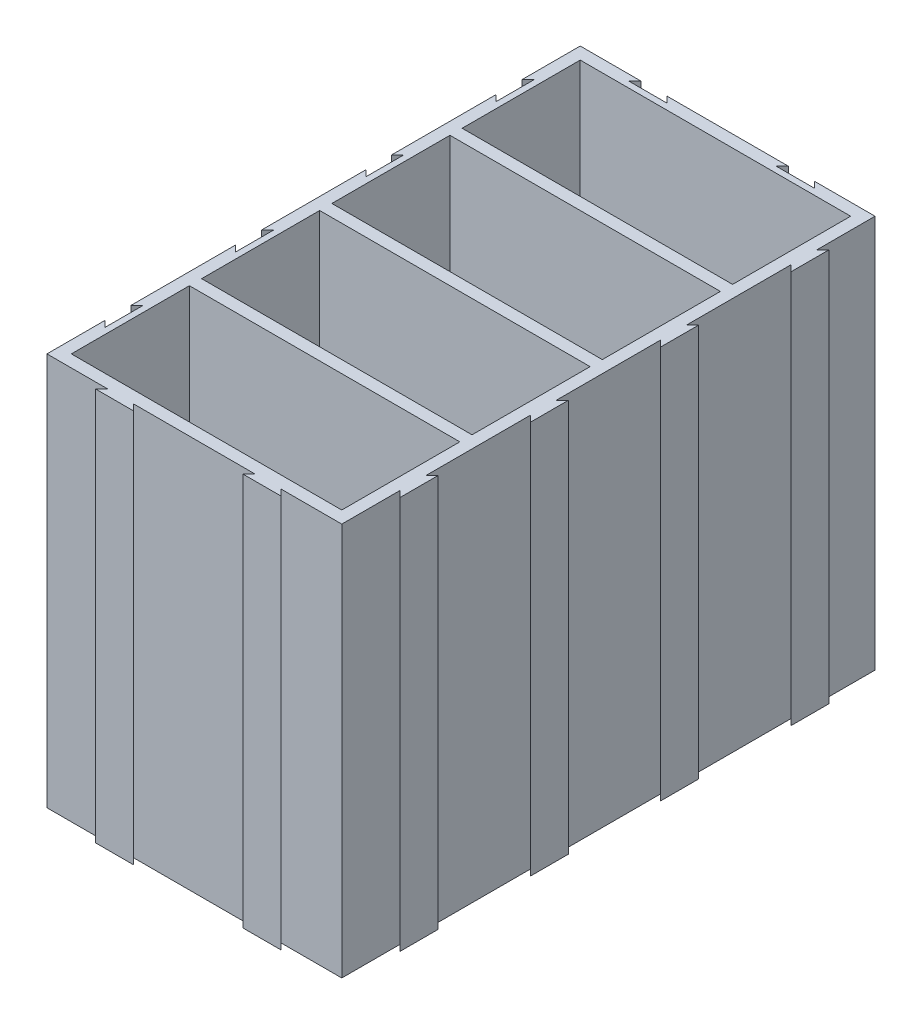
SolidWorks part; units mm, degrees
ref_plane "Спереди" through (0, 0, 0) normal (0, 0, 1) x (1, 0, 0)
ref_plane "Сверху" through (0, 0, 0) normal (0, 1, 0) x (1, 0, 0)
ref_plane "Справа" through (0, 0, 0) normal (1, 0, 0) x (0, 0, -1)
sketch "Эскиз1" plane through (0, 0, 0) normal (0, 1, 0) x (1, 0, 0)
  line L0 (0, 24.2143) -> (0, -22.6471) construction
  line L1 (0, -8.55) -> (0, 8.55) construction
  line L2 (-17.75, 0.8) -> (17.75, 0.8)
  line L3 (-17.75, 0.8) -> (-17.75, 16.3)
  line L4 (-17.75, 16.3) -> (17.75, 16.3)
  line L5 (17.75, 0.8) -> (17.75, 16.3)
  line L6 (-17.75, 0.8) -> (17.75, 16.3) construction
  line L7 (-17.75, 16.3) -> (17.75, 0.8) construction
  line L8 (-17.75, 17.9) -> (17.75, 17.9)
  line L9 (-17.75, 17.9) -> (-17.75, 33.4)
  line L10 (-17.75, 33.4) -> (17.75, 33.4)
  line L11 (17.75, 17.9) -> (17.75, 33.4)
  line L12 (-17.75, 17.9) -> (17.75, 33.4) construction
  line L13 (-17.75, 33.4) -> (17.75, 17.9) construction
  line L14 (-17.75, -16.3) -> (17.75, -16.3)
  line L15 (-17.75, -16.3) -> (-17.75, -0.8)
  line L16 (-17.75, -0.8) -> (17.75, -0.8)
  line L17 (17.75, -16.3) -> (17.75, -0.8)
  line L18 (-17.75, -16.3) -> (17.75, -0.8) construction
  line L19 (-17.75, -0.8) -> (17.75, -16.3) construction
  line L20 (-17.75, -33.4) -> (17.75, -33.4)
  line L21 (-17.75, -33.4) -> (-17.75, -17.9)
  line L22 (-17.75, -17.9) -> (17.75, -17.9)
  line L23 (17.75, -33.4) -> (17.75, -17.9)
  line L24 (-17.75, -33.4) -> (17.75, -17.9) construction
  line L25 (-17.75, -17.9) -> (17.75, -33.4) construction
  line L26 (-19.35, 27.35) -> (-18.55, 28.15)
  line L27 (-19.35, 35) -> (-11.375, 35)
  line L28 (-19.35, 35) -> (-19.35, 27.35)
  line L29 (-19.35, -35) -> (-11.375, -35)
  line L30 (19.35, 35) -> (19.35, 27.35)
  line L31 (-18.55, 28.15) -> (-18.55, 23.15)
  line L32 (-18.55, 23.15) -> (-19.35, 23.95)
  line L33 (20.15, 28.15) -> (20.15, 23.15)
  line L34 (19.35, 27.35) -> (20.15, 28.15)
  line L35 (20.15, 23.15) -> (19.35, 23.95)
  line L36 (20.15, 11.05) -> (20.15, 6.05)
  line L37 (19.35, 10.25) -> (20.15, 11.05)
  line L38 (20.15, 6.05) -> (19.35, 6.85)
  line L39 (20.15, -6.05) -> (20.15, -11.05)
  line L40 (19.35, -6.85) -> (20.15, -6.05)
  line L41 (20.15, -11.05) -> (19.35, -10.25)
  line L42 (20.15, -23.15) -> (20.15, -28.15)
  line L43 (19.35, -23.95) -> (20.15, -23.15)
  line L44 (20.15, -28.15) -> (19.35, -27.35)
  line L45 (-18.55, 11.05) -> (-18.55, 6.05)
  line L46 (-19.35, 10.25) -> (-18.55, 11.05)
  line L47 (-18.55, 6.05) -> (-19.35, 6.85)
  line L48 (-18.55, -6.05) -> (-18.55, -11.05)
  line L49 (-19.35, -6.85) -> (-18.55, -6.05)
  line L50 (-18.55, -11.05) -> (-19.35, -10.25)
  line L51 (-18.55, -23.15) -> (-18.55, -28.15)
  line L52 (-19.35, -23.95) -> (-18.55, -23.15)
  line L53 (-18.55, -28.15) -> (-19.35, -27.35)
  line L54 (-19.35, 23.95) -> (-19.35, 10.25)
  line L55 (-19.35, 6.85) -> (-19.35, -6.85)
  line L56 (-19.35, -10.25) -> (-19.35, -23.95)
  line L57 (-19.35, -27.35) -> (-19.35, -35)
  line L58 (19.35, -27.35) -> (19.35, -35)
  line L59 (19.35, -10.25) -> (19.35, -23.95)
  line L60 (19.35, 6.85) -> (19.35, -6.85)
  line L61 (19.35, 23.95) -> (19.35, 10.25)
  line L62 (11.375, -35) -> (12.175, -35.8)
  line L63 (12.175, -35.8) -> (7.175, -35.8)
  line L64 (7.175, -35.8) -> (7.975, -35)
  line L65 (-7.175, -35.8) -> (-12.175, -35.8)
  line L66 (-12.175, -35.8) -> (-11.375, -35)
  line L67 (-7.975, -35) -> (-7.175, -35.8)
  line L68 (-7.175, 34.2) -> (-12.175, 34.2)
  line L69 (-12.175, 34.2) -> (-11.375, 35)
  line L70 (-7.975, 35) -> (-7.175, 34.2)
  line L71 (12.175, 34.2) -> (7.175, 34.2)
  line L72 (7.175, 34.2) -> (7.975, 35)
  line L73 (11.375, 35) -> (12.175, 34.2)
  line L74 (-7.975, -35) -> (7.975, -35)
  line L75 (11.375, -35) -> (19.35, -35)
  line L76 (11.375, 35) -> (19.35, 35)
  line L77 (-7.975, 35) -> (7.975, 35)
  line L78 (-16.75, 28.15) -> (-3.5, 28.15)
  line L79 (-2.5, 32.4) -> (-2.5, 29.15)
  line L80 (2.5, 32.4) -> (2.5, 29.15)
  line L81 (16.75, 28.15) -> (3.5, 28.15)
  line L82 (-16.75, 23.15) -> (-3.5, 23.15)
  line L83 (-2.5, 18.9) -> (-2.5, 22.15)
  line L84 (2.5, 18.9) -> (2.5, 22.15)
  line L85 (16.75, 23.15) -> (3.5, 23.15)
  line L86 (-2.5, 1.8) -> (-2.5, 5.05)
  line L87 (-16.75, 6.05) -> (-3.5, 6.05)
  line L88 (-2.5, 15.3) -> (-2.5, 12.05)
  line L89 (-16.75, 11.05) -> (-3.5, 11.05)
  line L90 (2.5, 15.3) -> (2.5, 12.05)
  line L91 (16.75, 11.05) -> (3.5, 11.05)
  line L92 (16.75, 6.05) -> (3.5, 6.05)
  line L93 (2.5, 1.8) -> (2.5, 5.05)
  line L94 (-2.5, -15.3) -> (-2.5, -12.05)
  line L95 (-16.75, -11.05) -> (-3.5, -11.05)
  line L96 (-2.5, -1.8) -> (-2.5, -5.05)
  line L97 (-16.75, -6.05) -> (-3.5, -6.05)
  line L98 (2.5, -1.8) -> (2.5, -5.05)
  line L99 (16.75, -6.05) -> (3.5, -6.05)
  line L100 (16.75, -11.05) -> (3.5, -11.05)
  line L101 (2.5, -15.3) -> (2.5, -12.05)
  line L102 (-2.5, -32.4) -> (-2.5, -29.15)
  line L103 (-16.75, -28.15) -> (-3.5, -28.15)
  line L104 (-2.5, -18.9) -> (-2.5, -22.15)
  line L105 (-16.75, -23.15) -> (-3.5, -23.15)
  line L106 (2.5, -18.9) -> (2.5, -22.15)
  line L107 (16.75, -23.15) -> (3.5, -23.15)
  line L108 (16.75, -28.15) -> (3.5, -28.15)
  line L109 (2.5, -32.4) -> (2.5, -29.15)
  arc A0 (-16.75, 33.4) -> (-17.75, 32.4) centre (-16.75, 32.4) ccw
  arc A1 (-2.5, 32.4) -> (-3.5, 33.4) centre (-3.5, 32.4) ccw
  arc A2 (3.5, 33.4) -> (2.5, 32.4) centre (3.5, 32.4) ccw
  arc A3 (2.5, 18.9) -> (3.5, 17.9) centre (3.5, 18.9) ccw
  arc A4 (-3.5, 17.9) -> (-2.5, 18.9) centre (-3.5, 18.9) ccw
  arc A5 (-17.75, 18.9) -> (-16.75, 17.9) centre (-16.75, 18.9) ccw
  arc A6 (17.75, 32.4) -> (16.75, 33.4) centre (16.75, 32.4) ccw
  arc A7 (16.75, 17.9) -> (17.75, 18.9) centre (16.75, 18.9) ccw
  arc A8 (-17.75, 29.15) -> (-16.75, 28.15) centre (-16.75, 29.15) ccw
  arc A9 (-16.75, 23.15) -> (-17.75, 22.15) centre (-16.75, 22.15) ccw
  arc A10 (-3.5, 28.15) -> (-2.5, 29.15) centre (-3.5, 29.15) ccw
  arc A11 (-2.5, 22.15) -> (-3.5, 23.15) centre (-3.5, 22.15) ccw
  arc A12 (2.5, 29.15) -> (3.5, 28.15) centre (3.5, 29.15) ccw
  arc A13 (3.5, 23.15) -> (2.5, 22.15) centre (3.5, 22.15) ccw
  arc A14 (16.75, 28.15) -> (17.75, 29.15) centre (16.75, 29.15) ccw
  arc A15 (17.75, 22.15) -> (16.75, 23.15) centre (16.75, 22.15) ccw
  arc A16 (-3.5, 0.8) -> (-2.5, 1.8) centre (-3.5, 1.8) ccw
  arc A17 (-2.5, 5.05) -> (-3.5, 6.05) centre (-3.5, 5.05) ccw
  arc A18 (-17.75, 1.8) -> (-16.75, 0.8) centre (-16.75, 1.8) ccw
  arc A19 (-16.75, 6.05) -> (-17.75, 5.05) centre (-16.75, 5.05) ccw
  arc A20 (-17.75, 12.05) -> (-16.75, 11.05) centre (-16.75, 12.05) ccw
  arc A21 (-16.75, 16.3) -> (-17.75, 15.3) centre (-16.75, 15.3) ccw
  arc A22 (-2.5, 15.3) -> (-3.5, 16.3) centre (-3.5, 15.3) ccw
  arc A23 (-3.5, 11.05) -> (-2.5, 12.05) centre (-3.5, 12.05) ccw
  arc A24 (2.5, 12.05) -> (3.5, 11.05) centre (3.5, 12.05) ccw
  arc A25 (3.5, 16.3) -> (2.5, 15.3) centre (3.5, 15.3) ccw
  arc A26 (16.75, 11.05) -> (17.75, 12.05) centre (16.75, 12.05) ccw
  arc A27 (17.75, 15.3) -> (16.75, 16.3) centre (16.75, 15.3) ccw
  arc A28 (16.75, 0.8) -> (17.75, 1.8) centre (16.75, 1.8) ccw
  arc A29 (17.75, 5.05) -> (16.75, 6.05) centre (16.75, 5.05) ccw
  arc A30 (3.5, 6.05) -> (2.5, 5.05) centre (3.5, 5.05) ccw
  arc A31 (2.5, 1.8) -> (3.5, 0.8) centre (3.5, 1.8) ccw
  arc A32 (-3.5, -16.3) -> (-2.5, -15.3) centre (-3.5, -15.3) ccw
  arc A33 (-2.5, -12.05) -> (-3.5, -11.05) centre (-3.5, -12.05) ccw
  arc A34 (-17.75, -15.3) -> (-16.75, -16.3) centre (-16.75, -15.3) ccw
  arc A35 (-16.75, -11.05) -> (-17.75, -12.05) centre (-16.75, -12.05) ccw
  arc A36 (-17.75, -5.05) -> (-16.75, -6.05) centre (-16.75, -5.05) ccw
  arc A37 (-16.75, -0.8) -> (-17.75, -1.8) centre (-16.75, -1.8) ccw
  arc A38 (-2.5, -1.8) -> (-3.5, -0.8) centre (-3.5, -1.8) ccw
  arc A39 (-3.5, -6.05) -> (-2.5, -5.05) centre (-3.5, -5.05) ccw
  arc A40 (2.5, -5.05) -> (3.5, -6.05) centre (3.5, -5.05) ccw
  arc A41 (3.5, -0.8) -> (2.5, -1.8) centre (3.5, -1.8) ccw
  arc A42 (16.75, -6.05) -> (17.75, -5.05) centre (16.75, -5.05) ccw
  arc A43 (17.75, -1.8) -> (16.75, -0.8) centre (16.75, -1.8) ccw
  arc A44 (16.75, -16.3) -> (17.75, -15.3) centre (16.75, -15.3) ccw
  arc A45 (17.75, -12.05) -> (16.75, -11.05) centre (16.75, -12.05) ccw
  arc A46 (3.5, -11.05) -> (2.5, -12.05) centre (3.5, -12.05) ccw
  arc A47 (2.5, -15.3) -> (3.5, -16.3) centre (3.5, -15.3) ccw
  arc A48 (-3.5, -33.4) -> (-2.5, -32.4) centre (-3.5, -32.4) ccw
  arc A49 (-2.5, -29.15) -> (-3.5, -28.15) centre (-3.5, -29.15) ccw
  arc A50 (-17.75, -32.4) -> (-16.75, -33.4) centre (-16.75, -32.4) ccw
  arc A51 (-16.75, -28.15) -> (-17.75, -29.15) centre (-16.75, -29.15) ccw
  arc A52 (-17.75, -22.15) -> (-16.75, -23.15) centre (-16.75, -22.15) ccw
  arc A53 (-16.75, -17.9) -> (-17.75, -18.9) centre (-16.75, -18.9) ccw
  arc A54 (-2.5, -18.9) -> (-3.5, -17.9) centre (-3.5, -18.9) ccw
  arc A55 (-3.5, -23.15) -> (-2.5, -22.15) centre (-3.5, -22.15) ccw
  arc A56 (2.5, -22.15) -> (3.5, -23.15) centre (3.5, -22.15) ccw
  arc A57 (3.5, -17.9) -> (2.5, -18.9) centre (3.5, -18.9) ccw
  arc A58 (16.75, -23.15) -> (17.75, -22.15) centre (16.75, -22.15) ccw
  arc A59 (17.75, -18.9) -> (16.75, -17.9) centre (16.75, -18.9) ccw
  arc A60 (16.75, -33.4) -> (17.75, -32.4) centre (16.75, -32.4) ccw
  arc A61 (17.75, -29.15) -> (16.75, -28.15) centre (16.75, -29.15) ccw
  arc A62 (3.5, -28.15) -> (2.5, -29.15) centre (3.5, -29.15) ccw
  arc A63 (2.5, -32.4) -> (3.5, -33.4) centre (3.5, -32.4) ccw
  point P1 (0, 8.55)
  point P8 (0, 25.65)
  point P13 (0, -8.55)
  point P18 (0, -25.65)
  point P26 (0, 0)
  point P32 (-18.55, 25.65)
  point P66 (9.675, -35.8)
  point P68 (-9.675, -35.8)
  dimension "D25" = 1
  dimension "D1" = 35.5
  dimension "D2" = 15.5
  dimension "D3" = 1.6
  dimension "D4" = 1.6
  dimension "D5" = 1.6
  dimension "D6" = 1.6
  dimension "D7" = 1.6
  dimension "D8" = 1.6
  dimension "D9" = 1.6
  dimension "D10" = 5
  dimension "D11" = 45
  dimension "D12" = 0.8
  dimension "D15" = 0.8
  dimension "D16" = 5
  dimension "D17" = 45
  dimension "D18" = 9.675
  dimension "D21" = 5
  dimension "D22" = 2.5
  dimension "D23" = 5
  dimension "D24" = 2.5
  dimension "D13" = 2
  dimension "D14" = 4
  dimension "D19" = 2
  dimension "D20" = 2
  dimension "D26" = 4
extrude "Бобышка-Вытянуть1" add sketch "Эскиз1" along normal blind 1.6 contours L77 L70 L68 L69 L27 L28 L26 L31 L32 L54 L46 L45 L47 L55 L49 L48 L50 L56 L52 L51 L53 L57 L29 L66 L65 L67 L74 L64 L63 L62 L75 L58 L44 L42 L43 L59 L41 L39 L40 L60 L38 L36 L37 L61 L35 L33 L34 L30 L76 L73 L71 | A63 L109 A62 L108 A61 L23 A58 L107 A56 L106 A57 L22 A54 L104 A55 L105 A52 L21 A51 L103 A49 L102 A48 L20 | A47 L101 A46 L100 A45 L17 A42 L99 A40 L98 A41 L16 A38 L96 A39 L97 A36 L15 A35 L95 A33 L94 A32 L14 | A31 L93 A30 L92 A29 L5 A26 L91 A24 L90 A25 L4 A22 L88 A23 L89 A20 L3 A19 L87 A17 L86 A16 L2 | A15 L11 A14 L81 A12 L80 A2 L10 A1 L79 A10 L78 A8 L9 A9 L82 A11 L83 A4 L8 A3 L84 A13 L85 | A0 L10 L9 | A6 L11 L10 | A7 L8 L11 | A27 L5 L4 | A28 L2 L5 | A43 L17 L16 | A44 L14 L17 | A59 L23 L22 | A60 L20 L23 | A50 L21 L20 | A34 L15 L14 | A53 L22 L21 | A18 L3 L2 | A37 L16 L15 | A5 L9 L8 | A21 L4 L3 region at (-17.5266, 0, -1.0234) region at (0, 0, -8.55) region at (17.5266, 0, -1.0234) region at (-17.5266, 0, -16.0766) region at (17.5266, 0, -16.0766) region at (-17.5266, 0, -18.1234) region at (0, 0, -25.65) region at (17.5266, 0, -18.1234) region at (-17.5266, 0, -33.1766) region at (17.5266, 0, -33.1766) region at (-17.5266, 0, 16.0766) region at (0, 0, 8.55) region at (17.5266, 0, 16.0766) region at (-17.5266, 0, 1.0234) region at (17.5266, 0, 1.0234) region at (-17.5266, 0, 33.1766) region at (0, 0, 25.65) region at (17.5266, 0, 33.1766) region at (-17.5266, 0, 18.1234) region at (17.5266, 0, 18.1234) region at (-18.5393, 0, -31.175)
extrude "Бобышка-Вытянуть2" add sketch "Эскиз1<3>" along normal blind 50 from offset 1.6 contours L77 L70 L68 L69 L27 L28 L26 L31 L32 L54 L46 L45 L47 L55 L49 L48 L50 L56 L52 L51 L53 L57 L29 L66 L65 L67 L74 L64 L63 L62 L75 L58 L44 L42 L43 L59 L41 L39 L40 L60 L38 L36 L37 L61 L35 L33 L34 L30 L76 L73 L71 region at (-18.5393, 0, -31.175)
sketch "Эскиз1<3>" plane through (0, 0, 0) normal (0, 1, 0) x (1, 0, 0) same geometry as "Эскиз1"
equation "\"D18@Эскиз1\"=(35.5+1.6*2)/4"
